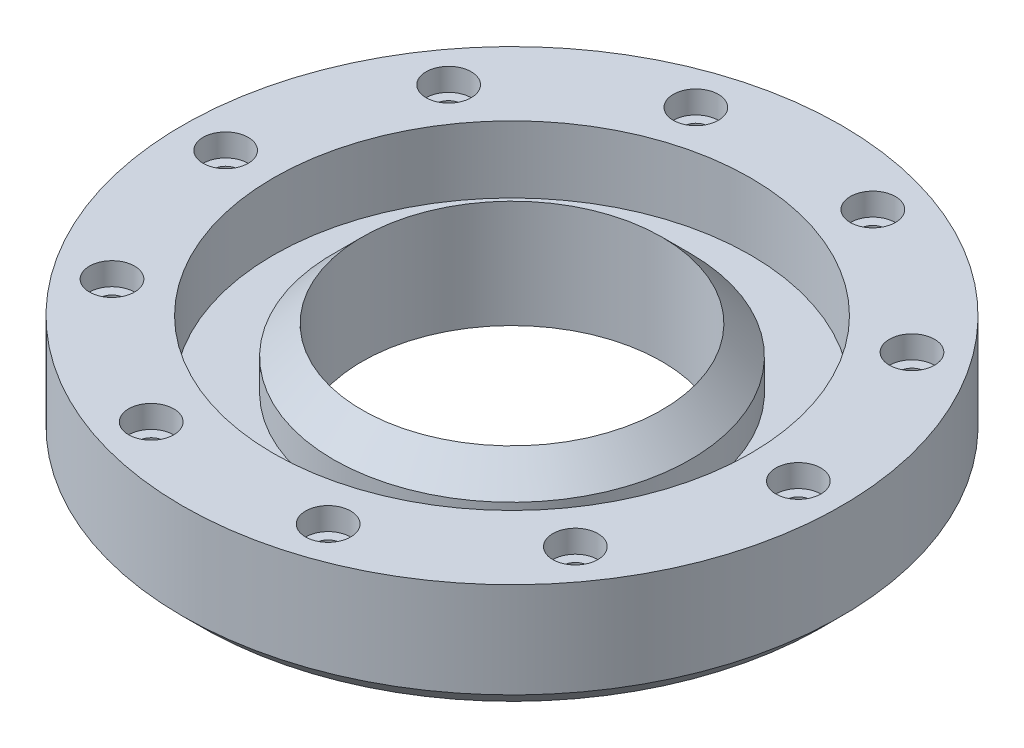
SolidWorks part; units mm, degrees
material "Nickel"
ref_plane "Front Plane" through (0, 0, 0) normal (0, 0, 1) x (1, 0, 0)
ref_plane "Top Plane" through (0, 0, 0) normal (0, 1, 0) x (1, 0, 0)
ref_plane "Right Plane" through (0, 0, 0) normal (1, 0, 0) x (0, 0, -1)
sketch "Sketch1" plane through (0, 0, 0) normal (0, 0, 1) x (1, 0, 0)
  line L0 (0, 0) -> (0, 36.0255) construction
  line L1 (19.939, 0) -> (43.848, 0)
  line L2 (19.939, 0) -> (19.939, 14.3332) construction
  line L3 (31.75, 6.35) -> (31.75, 15.24)
  line L4 (23.749, 6.35) -> (31.75, 6.35)
  line L5 (31.75, 15.24) -> (43.848, 15.24)
  line L6 (23.749, 14.3332) -> (23.749, 6.35)
  line L7 (19.939, 14.3332) -> (23.749, 14.3332)
  line L9 (19.939, 0) -> (19.939, 14.3332)
  line L12 (43.848, 0) -> (43.848, 15.24)
  dimension "D1" = 43.848
  dimension "D2" = 19.939
  dimension "D3" = 3.81
  dimension "D4" = 6.35
  dimension "D5" = 31.75
  dimension "D6" = 7.9832
  dimension "D7" = 8.89
revolve "Revolve1" add sketch "Sketch1" angle 360 about L0
chamfer "Chamfer2" distance 3.81 angle 45 1 edges at (0, 14.3332, -23.749)
hole_wizard "Hole1" positions "Sketch2" profile "Sketch3" legacy
sketch "Sketch2" plane through (0, 15.24, 0) normal (0, 1, 0) x (1, 0, 0)
  line L0 (38.1, 0) -> (0, 0) construction
  point P0 (38.1, 0)
  dimension "D1" = 38.1
sketch "Sketch3" plane through (38.1, 15.24, 0) normal (1, 0, 0) x (0, 0, 1)
  line L0 (0, 0) -> (0, 3)
  line L1 (0, 3) -> (3, 3)
  line L2 (3, 3) -> (3, 0)
  line L3 (3, 0) -> (0, 0)
  line L4 (0, 110) -> (0, -10) construction
  dimension "Diameter" = 6
  dimension "Depth" = 3
hole_wizard "M4x0.7 Tapped Hole1" positions "Sketch4" profile "Sketch5" tap size "M4x0.7" standard "ANSI Metric"
sketch "Sketch4" plane through (0, 12.24, 0) normal (0, 1, 0) x (1, 0, 0)
  circle A0 centre (38.1, 0) radius 3 construction
  circle A1 centre (38.1, 0) radius 3
  point P0 (38.1, 0)
sketch "Sketch5" plane through (38.1, 12.24, 0) normal (1, 0, 0) x (0, 0, 1)
  line L0 (0, 0) -> (0, 8.9914)
  line L1 (0, 8.9914) -> (1.65, 8)
  line L2 (1.65, 8) -> (1.65, 0)
  line L5 (1.65, 0) -> (0, 0)
  line L10 (0, 8.9914) -> (-1.65, 8) construction
  line L11 (0, -6.35) -> (0, 107.95) construction
  dimension "Tap Drill Dia." = 3.3
  dimension "Tap Drill Depth" = 8
  dimension "Drill Angle" = 118
cosmetic thread "Hole Thread1" parameters "D1"=7.874, "D2"=4
pattern_circular "CirPattern1" count 10 over 360 about axis through (0, 15.24, 0) along (0, -1, 0) of "M4x0.7 Tapped Hole1", "Hole1"
chamfer "Chamfer3" distance 2.54 angle 45 1 edges at (0, 0, -43.848)
